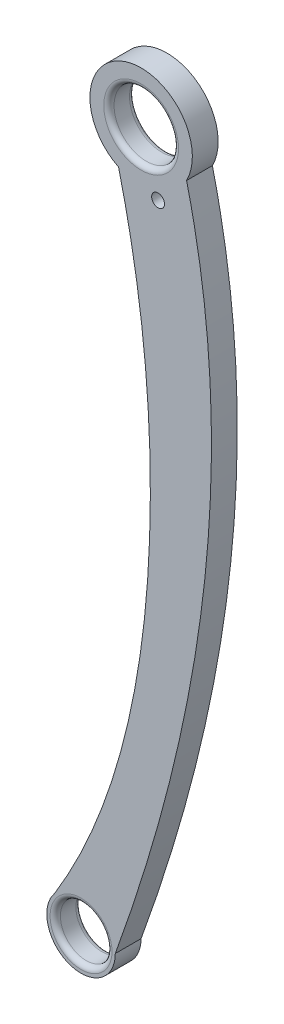
SolidWorks part; units mm, degrees
ref_plane "Front Plane" through (0, 0, 0) normal (0, 0, 1) x (1, 0, 0)
ref_plane "Top Plane" through (0, 0, 0) normal (0, 1, 0) x (1, 0, 0)
ref_plane "Right Plane" through (0, 0, 0) normal (1, 0, 0) x (0, 0, -1)
sketch "Sketch1" plane through (0, 0, 0) normal (0, 0, 1) x (1, 0, 0)
  circle A4 centre (9.3211, 113.0271) radius 5
  circle A5 centre (0, 0) radius 4
  circle A6 centre (0, 0) radius 5.3116
  circle A7 centre (9.3211, 113.0271) radius 5.8831
  circle A8 centre (11.9499, 104.4783) radius 1
  circle A9 centre (9.3211, 113.0271) radius 7.9439
  spline S0 degree 3 poles (5.3116, 0) (18.3322, 35.977) (25.8525, 76.6433) (15.0739, 114.2585) knots 0 0 0 0 1 1 1 1
  spline S1 degree 3 poles (-4.0924, 3.3861) (6.9948, 21.5779) (13.3983, 58.8073) (8.8854, 94.5824) (5.0114, 109.0226) knots 0 0 0 0 0.587614 1 1 1 1
  dimension "D1" = 10
  dimension "D3" = 8
extrude "Boss-Extrude1" add sketch "Sketch1" along normal mid plane 4 contours S1 A6 S0 A7 A8 | A6 A5 | S1 A9 S0 A7 | A9 S1 A7 S0 | A7 A4 region at (-1.7486, -4.8562, 0) region at (12.2378, 57.8881, 0) region at (15.9583, 111.8739, 0) region at (14.3144, 107.0376, 0) region at (15.0061, 113.6288, 0)
fillet "Fillet1" radius 0.8 4 edges at (4, 0, -2) (4, 0, 2) (14.3211, 113.0271, -2) (14.3211, 113.0271, 2)
